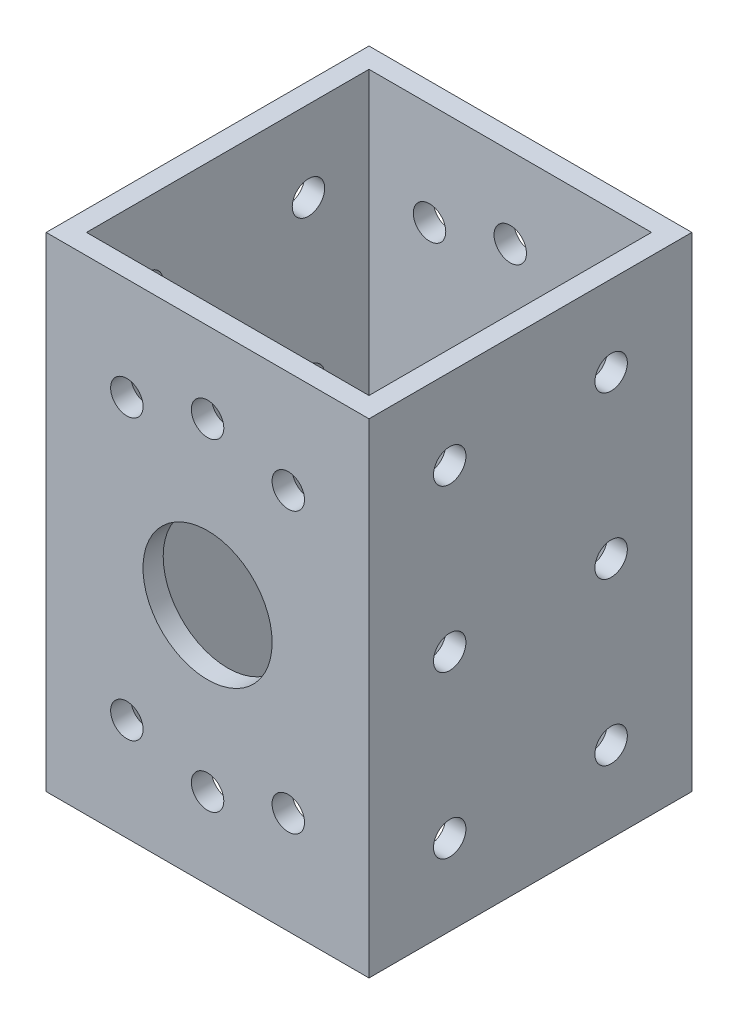
SolidWorks part; units mm, degrees
ref_plane "Front Plane" through (0, 0, 0) normal (0, 0, 1) x (1, 0, 0)
ref_plane "Top Plane" through (0, 0, 0) normal (0, 1, 0) x (1, 0, 0)
ref_plane "Right Plane" through (0, 0, 0) normal (1, 0, 0) x (0, 0, -1)
sketch "Sketch1" plane through (0, 0, 0) normal (0, 1, 0) x (1, 0, 0)
  line L1 (-25.4, -25.4) -> (25.4, -25.4)
  line L2 (-25.4, -25.4) -> (-25.4, 25.4)
  line L3 (-25.4, 25.4) -> (25.4, 25.4)
  line L4 (25.4, -25.4) -> (25.4, 25.4)
  line L5 (-25.4, -25.4) -> (25.4, 25.4) construction
  line L6 (-25.4, 25.4) -> (25.4, -25.4) construction
  line L11 (-22.225, -22.225) -> (22.225, -22.225)
  line L12 (-22.225, -22.225) -> (-22.225, 22.225)
  line L13 (-22.225, 22.225) -> (22.225, 22.225)
  line L14 (22.225, -22.225) -> (22.225, 22.225)
  line L15 (-22.225, -22.225) -> (22.225, 22.225) construction
  line L16 (-22.225, 22.225) -> (22.225, -22.225) construction
  point P0 (0, 0)
  point P6 (0, 0)
  dimension "D1" = 50.8
  dimension "D2" = 50.8
  dimension "D3" = 3.175
  dimension "D4" = 3.175
extrude "Boss-Extrude1" add sketch "Sketch1" along normal blind 76.2
sketch "Sketch2" plane through (0, 0, 25.4) normal (0, 0, 1) x (1, 0, 0)
  line L0 (-25.4, 0) -> (25.4, 0) construction
  line L1 (25.4, 76.2) -> (25.4, 0) construction
  circle A0 centre (0, 38.1) radius 25.4
  dimension "D1" = 50.8
  dimension "D2" = 38.1
  dimension "D3" = 25.4
sketch "Sketch3" plane through (0, 0, 25.4) normal (0, 0, 1) x (1, 0, 0)
  circle A0 centre (0, 12.7) radius 2.5527
  circle A1 centre (0, 38.1) radius 25.4 construction
  dimension "D1" = 5.1054
extrude "Cut-Extrude1" cut sketch "Sketch3" against normal blind 50.8
ref_axis "Axis1" through (0, 38.1, 25.4) along (0, 0, 1)
pattern_circular "CirPattern1" count 12 every 30 about axis through (0, 38.1, 25.4) along (0, 0, 1) skipping 2, 3, 4, 8, 9, 10 of "Cut-Extrude1"
sketch "Sketch4" plane through (0, 0, 25.4) normal (0, 0, 1) x (1, 0, 0)
  circle A0 centre (0, 38.1) radius 10.16
  dimension "D1" = 20.32
extrude "Cut-Extrude2" cut sketch "Sketch4" against normal blind 50.8
sketch "Sketch5" plane through (-25.4, 0, 0) normal (-1, 0, 0) x (0, 0, 1)
  line L0 (-25.4, 0) -> (25.4, 0) construction
  line L1 (-25.4, 76.2) -> (-25.4, 0) construction
  circle A0 centre (-12.7, 12.7) radius 2.5527
  dimension "D1" = 5.1054
  dimension "D2" = 12.7
  dimension "D3" = 12.7
extrude "Cut-Extrude3" cut sketch "Sketch5" against normal blind 50.8
pattern_linear "LPattern1" count 3 spacing 25.4 along (0, 1, 0) count 2 spacing 25.4 along (0, 0, 1) of "Cut-Extrude3"
